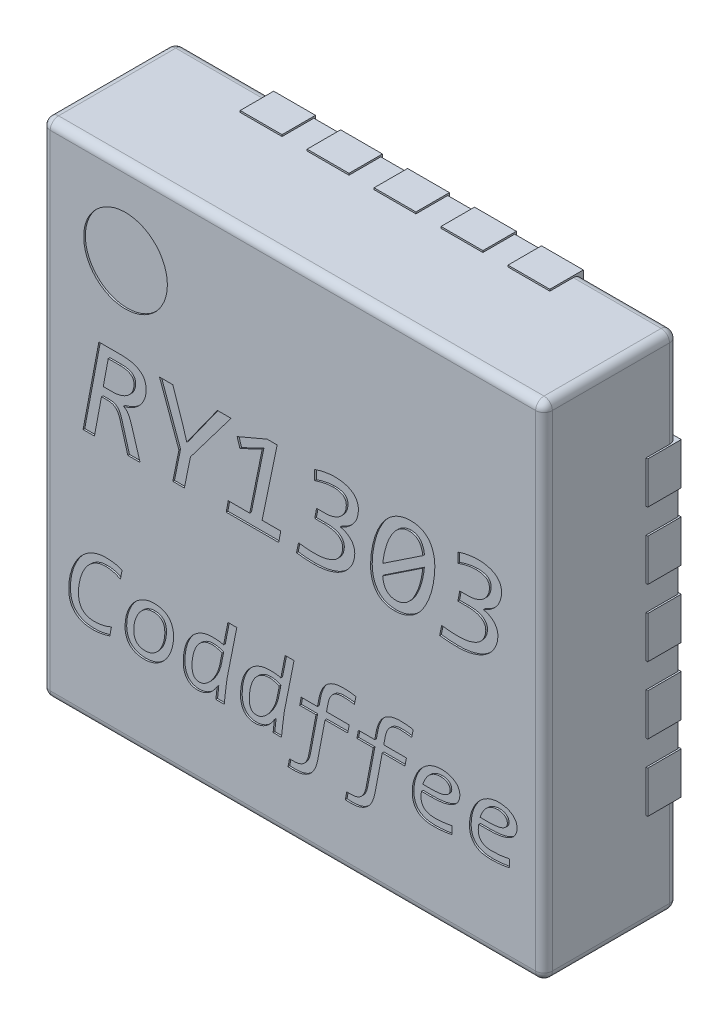
SolidWorks part; units mm, degrees
material "1023 碳钢板 (SS)"
ref_plane "前视基准面" through (0, 0, 0) normal (0, 0, 1) x (1, 0, 0)
ref_plane "上视基准面" through (0, 0, 0) normal (0, 1, 0) x (1, 0, 0)
ref_plane "右视基准面" through (0, 0, 0) normal (1, 0, 0) x (0, 0, -1)
ref_plane "芯片基底面" through (0, 0, 0.01) normal (0, 0, 1) x (1, 0, 0)
sketch "草图1" plane through (0, 0, 0.01) normal (0, 0, 1) x (1, 0, 0)
  line L1 (-1.5, 1.5) -> (1.5, 1.5)
  line L2 (-1.5, 1.5) -> (-1.5, -1.5)
  line L3 (-1.5, -1.5) -> (1.5, -1.5)
  line L4 (1.5, 1.5) -> (1.5, -1.5)
  line L5 (-1.5, 1.5) -> (1.5, -1.5) construction
  line L6 (-1.5, -1.5) -> (1.5, 1.5) construction
  point P0 (0, 0)
extrude "凸台-拉伸1" add sketch "草图1" along normal blind 0.8
sketch "草图3" plane through (0, 0, 0) normal (0, 0, 1) x (1, 0, 0)
  line L0 (0.525, 1.2) -> (0.275, 1.2)
  line L1 (0.525, 1.2) -> (0.525, 1.51)
  line L2 (0.925, 1.2) -> (0.675, 1.2)
  line L3 (0.925, 1.2) -> (0.925, 1.51)
  line L4 (0.925, 1.51) -> (0.675, 1.51)
  line L5 (0.675, 1.51) -> (0.675, 1.2)
  line L6 (0.525, 1.51) -> (0.275, 1.51)
  line L7 (0.275, 1.51) -> (0.275, 1.2)
  line L12 (0.125, 1.2) -> (-0.125, 1.2)
  line L13 (0.125, 1.2) -> (0.125, 1.51)
  line L14 (0.125, 1.51) -> (-0.125, 1.51)
  line L15 (-0.125, 1.51) -> (-0.125, 1.2)
  line L16 (-0.275, 1.2) -> (-0.525, 1.2)
  line L17 (-0.275, 1.2) -> (-0.275, 1.51)
  line L18 (-0.275, 1.51) -> (-0.525, 1.51)
  line L19 (-0.525, 1.51) -> (-0.525, 1.2)
  line L20 (-0.675, 1.2) -> (-0.925, 1.2)
  line L21 (-0.675, 1.2) -> (-0.675, 1.51)
  line L22 (-0.675, 1.51) -> (-0.925, 1.51)
  line L23 (-0.925, 1.51) -> (-0.925, 1.2)
  line L24 (1.2, -0.525) -> (1.2, -0.275)
  line L25 (1.2, -0.525) -> (1.51, -0.525)
  line L26 (1.2, -0.925) -> (1.2, -0.675)
  line L27 (1.2, -0.925) -> (1.51, -0.925)
  line L28 (1.51, -0.925) -> (1.51, -0.675)
  line L29 (1.51, -0.675) -> (1.2, -0.675)
  line L30 (1.51, -0.525) -> (1.51, -0.275)
  line L31 (1.51, -0.275) -> (1.2, -0.275)
  line L32 (1.2, -0.125) -> (1.2, 0.125)
  line L33 (1.2, -0.125) -> (1.51, -0.125)
  line L34 (1.51, -0.125) -> (1.51, 0.125)
  line L35 (1.51, 0.125) -> (1.2, 0.125)
  line L36 (1.2, 0.275) -> (1.2, 0.525)
  line L37 (1.2, 0.275) -> (1.51, 0.275)
  line L38 (1.51, 0.275) -> (1.51, 0.525)
  line L39 (1.51, 0.525) -> (1.2, 0.525)
  line L40 (1.2, 0.675) -> (1.2, 0.925)
  line L41 (1.2, 0.675) -> (1.51, 0.675)
  line L42 (1.51, 0.675) -> (1.51, 0.925)
  line L43 (1.51, 0.925) -> (1.2, 0.925)
  line L44 (-0.525, -1.2) -> (-0.275, -1.2)
  line L45 (-0.525, -1.2) -> (-0.525, -1.51)
  line L46 (-0.925, -1.2) -> (-0.675, -1.2)
  line L47 (-0.925, -1.2) -> (-0.925, -1.51)
  line L48 (-0.925, -1.51) -> (-0.675, -1.51)
  line L49 (-0.675, -1.51) -> (-0.675, -1.2)
  line L50 (-0.525, -1.51) -> (-0.275, -1.51)
  line L51 (-0.275, -1.51) -> (-0.275, -1.2)
  line L52 (-0.125, -1.2) -> (0.125, -1.2)
  line L53 (-0.125, -1.2) -> (-0.125, -1.51)
  line L54 (-0.125, -1.51) -> (0.125, -1.51)
  line L55 (0.125, -1.51) -> (0.125, -1.2)
  line L56 (0.275, -1.2) -> (0.525, -1.2)
  line L57 (0.275, -1.2) -> (0.275, -1.51)
  line L58 (0.275, -1.51) -> (0.525, -1.51)
  line L59 (0.525, -1.51) -> (0.525, -1.2)
  line L60 (0.675, -1.2) -> (0.925, -1.2)
  line L61 (0.675, -1.2) -> (0.675, -1.51)
  line L62 (0.675, -1.51) -> (0.925, -1.51)
  line L63 (0.925, -1.51) -> (0.925, -1.2)
  line L64 (-1.2, 0.525) -> (-1.2, 0.275)
  line L65 (-1.2, 0.525) -> (-1.51, 0.525)
  line L66 (-1.2, 0.925) -> (-1.2, 0.675)
  line L67 (-1.2, 0.925) -> (-1.51, 0.925)
  line L68 (-1.51, 0.925) -> (-1.51, 0.675)
  line L69 (-1.51, 0.675) -> (-1.2, 0.675)
  line L70 (-1.51, 0.525) -> (-1.51, 0.275)
  line L71 (-1.51, 0.275) -> (-1.2, 0.275)
  line L72 (-1.2, 0.125) -> (-1.2, -0.125)
  line L73 (-1.2, 0.125) -> (-1.51, 0.125)
  line L74 (-1.51, 0.125) -> (-1.51, -0.125)
  line L75 (-1.51, -0.125) -> (-1.2, -0.125)
  line L76 (-1.2, -0.275) -> (-1.2, -0.525)
  line L77 (-1.2, -0.275) -> (-1.51, -0.275)
  line L78 (-1.51, -0.275) -> (-1.51, -0.525)
  line L79 (-1.51, -0.525) -> (-1.2, -0.525)
  line L80 (-1.2, -0.675) -> (-1.2, -0.925)
  line L81 (-1.2, -0.675) -> (-1.51, -0.675)
  line L82 (-1.51, -0.675) -> (-1.51, -0.925)
  line L83 (-1.51, -0.925) -> (-1.2, -0.925)
  point P5 (0.8, 1.2)
  point P8 (0.4, 1.2)
  point P13 (0, 1.2)
  point P18 (-0.4, 1.2)
  point P23 (-0.8, 1.2)
  point P32 (1.2, -0.8)
  point P35 (1.2, -0.4)
  point P40 (1.2, 0)
  point P45 (1.2, 0.4)
  point P50 (1.2, 0.8)
  point P57 (-0.8, -1.2)
  point P60 (-0.4, -1.2)
  point P65 (0, -1.2)
  point P70 (0.4, -1.2)
  point P75 (0.8, -1.2)
  point P82 (-1.2, 0.8)
  point P85 (-1.2, 0.4)
  point P90 (-1.2, 0)
  point P95 (-1.2, -0.4)
  point P100 (-1.2, -0.8)
  point P103 (0, 0)
  dimension "D1" = 5
  dimension "D2" = 4
extrude "凸台-拉伸2" add sketch "草图3" along normal blind 0.2
sketch "草图4" plane through (0, 0, 0) normal (0, 0, 1) x (1, 0, 0)
  line L0 (-0.6, 0.9) -> (-0.9, 0.6)
  line L1 (0.9, 0.9) -> (-0.6, 0.9)
  line L2 (0.9, 0.9) -> (0.9, -0.9)
  line L3 (0.9, -0.9) -> (-0.9, -0.9)
  line L4 (-0.9, 0.6) -> (-0.9, -0.9)
  point P0 (0, 0)
extrude "凸台-拉伸3" add sketch "草图4" along normal blind 0.01
sketch "草图5" plane through (0, 0, 0.81) normal (0, 0, 1) x (1, 0, 0)
  line L0 (-1.5, 0) -> (1.5, 0) construction
  line L2 (-1.5, 1.5) -> (-1.5, -1.5) construction
  line L3 (1.5, -1.5) -> (1.5, 1.5) construction
  line L5 (-1.5, -1) -> (1.5, -1) construction
  circle A0 centre (-1, 1) radius 0.25
  text T0 "<i>RY1303</i>" font "Consolas" height 0.5
  text T1 "<i>Coddffee</i>" font "Consolas" height 0.4
  point P13 (0, -1)
extrude "切除-拉伸1" cut sketch "草图5" against normal blind 0.01
fillet "圆角1" radius 0.05 4 edges at (1.5, 1.5, 0.41) (1.5, -1.5, 0.41) (-1.5, -1.5, 0.41) (-1.5, 1.5, 0.41)
fillet "圆角2" radius 0.05 20 edges at (-1.1875, -1.5, 0.01) (-1.4854, -1.4854, 0.01) (1.1875, -1.5, 0.01) (1.4854, -1.4854, 0.01) (1.5, 1.1875, 0.01) (1.4854, 1.4854, 0.01) (-1.1875, 1.5, 0.01) (-1.4854, 1.4854, 0.01) (-1.4854, 1.4854, 0.81) (0, 1.5, 0.81) (1.4854, 1.4854, 0.81) (1.5, 0, 0.81) (1.4854, -1.4854, 0.81) (0, -1.5, 0.81) (-1.4854, -1.4854, 0.81) (-1.5, -1.1875, 0.01) (1.5, -1.1875, 0.01) (1.1875, 1.5, 0.01) (-1.5, 1.1875, 0.01) (-1.5, 0, 0.81)
